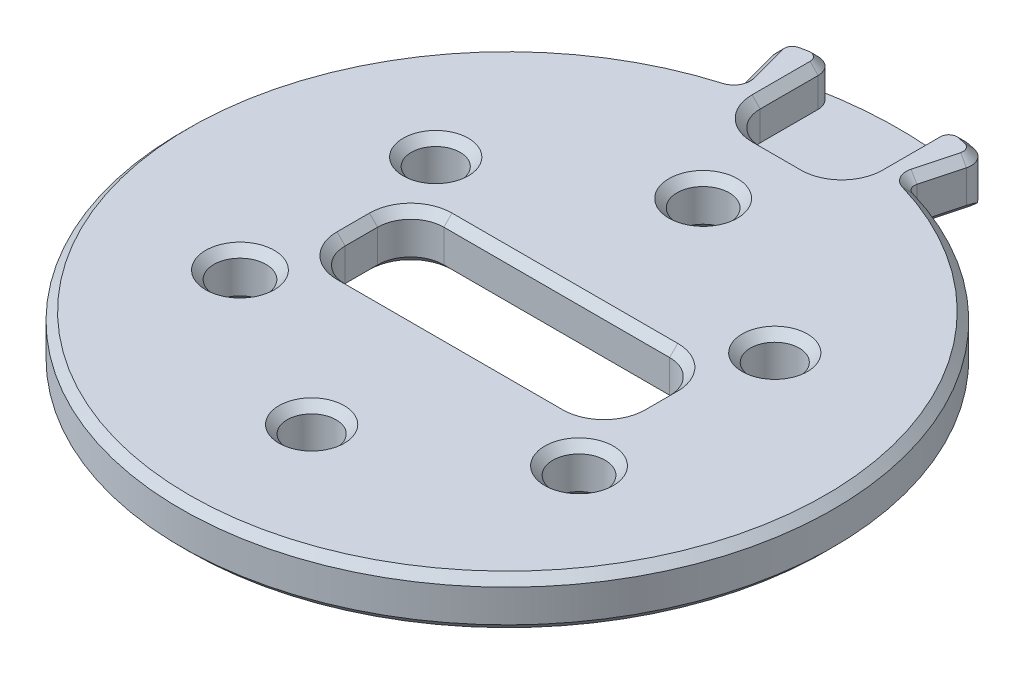
SolidWorks part; units mm, degrees
material "6061 合金"
ref_plane "前视基准面" through (0, 0, 0) normal (0, 0, 1) x (1, 0, 0)
ref_plane "上视基准面" through (0, 0, 0) normal (0, 1, 0) x (1, 0, 0)
ref_plane "右视基准面" through (0, 0, 0) normal (1, 0, 0) x (0, 0, -1)
other "Configuration Table"
sketch "草图1" plane through (0, 0, 0) normal (0, 1, 0) x (1, 0, 0)
  circle A0 centre (0, 0) radius 25
  dimension "D1" = 50
extrude "凸台-拉伸1" add sketch "草图1" along normal blind 3
sketch "草图2" plane through (0, 3, 0) normal (0, 1, 0) x (1, 0, 0)
  line L0 (0, 0) -> (0, -12) construction
  line L1 (0, 0) -> (10.3923, -6) construction
  circle A4 centre (0, 0) radius 12 construction
  circle A5 centre (10.3923, -6) radius 1.6
  circle A6 centre (-10.3923, -6) radius 1.6
  circle A7 centre (0, 12) radius 1.6
  circle A8 centre (0, -12) radius 1.5
  circle A9 centre (-10.3923, 6) radius 1.5
  circle A10 centre (10.3923, 6) radius 1.5
  point P12 (0, 0)
  point P14 (0, 0)
  point P20 (0, 0)
  dimension "D1" = 3.2
  dimension "D2" = 3
  dimension "D4" = 24
  dimension "D3" = 3
  dimension "D6" = 60
  dimension "D7" = 3
extrude "切除-拉伸1" cut sketch "草图2" against normal blind 3
sketch "草图3" plane through (0, 3, 0) normal (0, 1, 0) x (1, 0, 0)
  line L0 (0, 0) -> (0, 30) construction
  line L1 (0, 0) -> (-6.2117, 23.1822) construction
  line L2 (0, 0) -> (6.2117, 23.1822) construction
  line L3 (-6.2117, 23.1822) -> (-5.1764, 19.3185)
  line L4 (6.2117, 23.1822) -> (5.1764, 19.3185)
  arc A0 (-5.1764, 19.3185) -> (5.1764, 19.3185) centre (0, 0) ccw
  circle A3 centre (0, 0) radius 25 construction
  circle A4 centre (0, 0) radius 25
  arc A5 (6.2117, 23.1822) -> (-6.2117, 23.1822) centre (0, 0) ccw
  dimension "D1" = 40
  dimension "D3" = 48
  dimension "D2" = 30
  dimension "D4" = 15
extrude "切除-拉伸2" cut sketch "草图3" against normal blind 3
fillet "圆角1" radius 0.5 2 edges at (5.1764, 1.5, -19.3185) (-5.1764, 1.5, -19.3185)
sketch "草图4" plane through (0, 3, 0) normal (0, 1, 0) x (1, 0, 0)
  line L1 (-8.95, 3.025) -> (8.95, 3.025)
  line L2 (-8.95, 3.025) -> (-8.95, -3.025)
  line L3 (-8.95, -3.025) -> (8.95, -3.025)
  line L4 (8.95, 3.025) -> (8.95, -3.025)
  line L5 (-8.95, 3.025) -> (8.95, -3.025) construction
  line L6 (-8.95, -3.025) -> (8.95, 3.025) construction
  point P0 (0, 0)
  dimension "D1" = 6.05
  dimension "D2" = 17.9
extrude "切除-拉伸3" cut sketch "草图4" against normal blind 10
fillet "圆角3" radius 2.03 4 edges at (8.95, 1.5, 3.025) (8.95, 1.5, -3.025) (-8.95, 1.5, 3.025) (-8.95, 1.5, -3.025)
sketch "草图5" plane through (0, 3, 0) normal (0, 1, 0) x (1, 0, 0)
  line L0 (0, 0) -> (0, -15)
  line L2 (-3.5, 17) -> (3.5, 17)
  line L3 (-3.5, 17) -> (-3.5, 25)
  line L4 (-3.5, 25) -> (3.5, 25)
  line L5 (3.5, 17) -> (3.5, 25)
  line L6 (-3.5, 17) -> (3.5, 25) construction
  line L7 (-3.5, 25) -> (3.5, 17) construction
  point P6 (0, 21)
  dimension "D1" = 7
  dimension "D2" = 17
  dimension "D3" = 8
extrude "切除-拉伸5" cut sketch "草图5" against normal blind 2.3 contours L2 L5 L3 | L3 L2 L5 L4 region at (0, 3, -21)
fillet "圆角4" radius 2 2 edges at (3.5, 1.85, -17) (-3.5, 1.85, -17)
chamfer "倒角1" distance 0.5 angle 45 39 edges at (5.7579, 0, -21.4889) (-5.7579, 0, -21.4889) (5.3511, 0, -19.4215) (-5.3511, 0, -19.4215) (0, 0, 20) (5.7579, 3, -21.4889) (-5.7579, 3, -21.4889) (5.3511, 3, -19.4215) (-5.3511, 3, -19.4215) (0, 3, 20) (0, 0, -3.025) (-8.3554, 0, -2.4304) (8.3554, 0, -2.4304) (-8.95, 0, 0) (8.95, 0, 0) (-8.3554, 0, 2.4304) (8.3554, 0, 2.4304) (0, 0, 3.025) (10.3923, 0, 7.6) (0, 0, -10.4) (-10.3923, 0, 7.6) (0, 3, -3.025) (-8.3554, 3, -2.4304) (8.3554, 3, -2.4304) (-8.95, 3, 0) (8.95, 3, 0) (-8.3554, 3, 2.4304) (8.3554, 3, 2.4304) (0, 3, 3.025) (-10.3923, 3, 7.6) (0, 3, -10.4) (10.3923, 3, 7.6) (0, 0, 13.5) (-10.3923, 0, -4.5) (10.3923, 0, -4.5) (0, 3, 13.5) (10.3923, 3, -4.5) (-10.3923, 3, -4.5) (0, 0, -24)
fillet "圆角7" radius 1 4 edges at (-3.5, 1.85, -23.7434) (3.5, 1.85, -23.7434) (-6.2117, 1.5, -23.1822) (6.2117, 1.5, -23.1822)
chamfer "倒角3" distance 0.5 angle 45 11 edges at (4.947, 3, -23.4846) (3.8658, 3, -23.3287) (3.5, 3, -20.7777) (2.9142, 3, -17.5858) (0, 3, -17) (-2.9142, 3, -17.5858) (-3.5, 3, -20.7777) (-4.947, 3, -23.4846) (-3.8658, 3, -23.3287) (5.4623, 3, -23.3308) (-5.4623, 3, -23.3308)
